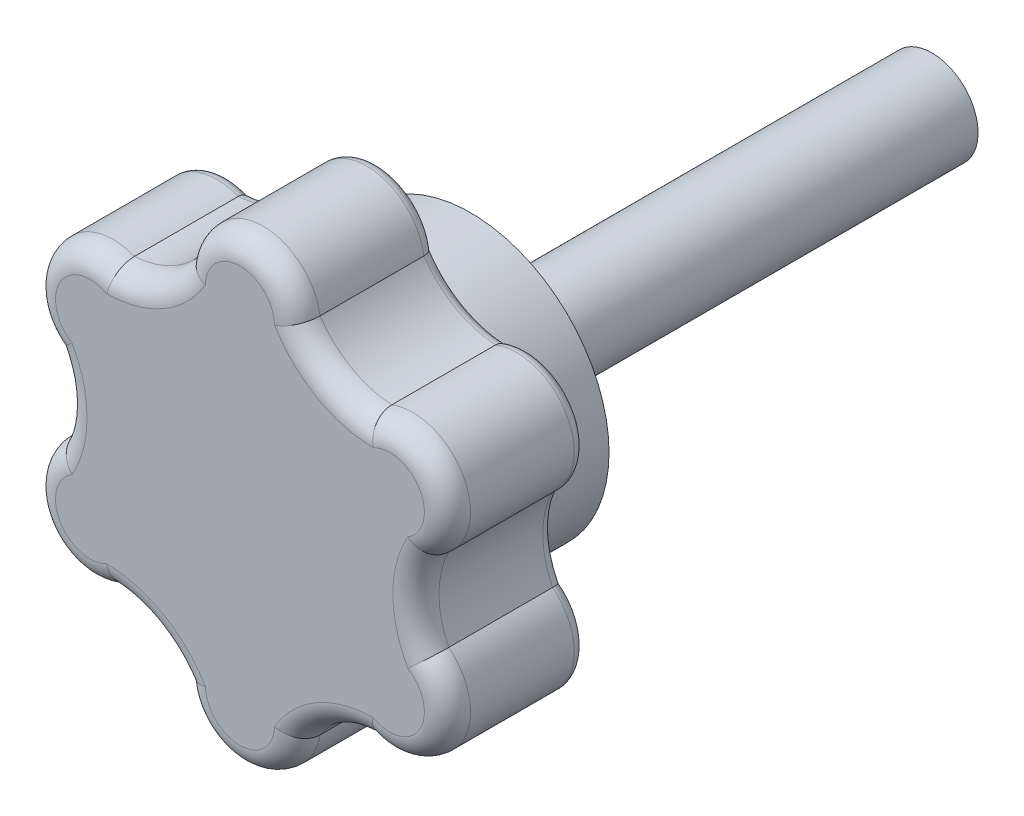
SolidWorks part; units mm, degrees
ref_plane "Front Plane" through (0, 0, 0) normal (0, 0, 1) x (1, 0, 0)
ref_plane "Top Plane" through (0, 0, 0) normal (0, 1, 0) x (1, 0, 0)
ref_plane "Right Plane" through (0, 0, 0) normal (1, 0, 0) x (0, 0, -1)
sketch "Sketch1" plane through (0, 0, 0) normal (0, 0, 1) x (1, 0, 0)
  line L0 (0, 0) -> (0, 28.3956) construction
  circle A0 centre (0, 0) radius 20 construction
  circle A1 centre (0, 0) radius 15 construction
  arc A2 (4.9469, 15.7265) -> (-4.9447, 15.7417) centre (0, 15) ccw
  arc A3 (16.093, 3.5791) -> (11.1603, 12.1531) centre (12.9904, 7.5) ccw
  arc A4 (11.1461, -12.1474) -> (16.105, -3.5886) centre (12.9904, -7.5) ccw
  arc A5 (-4.9469, -15.7265) -> (4.9447, -15.7417) centre (0, -15) ccw
  arc A6 (-16.093, -3.5791) -> (-11.1603, -12.1531) centre (-12.9904, -7.5) ccw
  arc A7 (-11.1461, 12.1474) -> (-16.105, 3.5886) centre (-12.9904, 7.5) ccw
  circle A8 centre (0, 0) radius 16.5 construction
  arc A9 (-16.093, -3.5791) -> (-16.105, 3.5886) centre (-23.289, -0.0073) ccw
  arc A10 (-11.1461, 12.1474) -> (-4.9447, 15.7417) centre (-11.6508, 20.1652) ccw
  arc A11 (4.9469, 15.7265) -> (11.1603, 12.1531) centre (11.6382, 20.1725) ccw
  arc A12 (16.093, 3.5791) -> (16.105, -3.5886) centre (23.289, 0.0073) ccw
  arc A13 (11.1461, -12.1474) -> (4.9447, -15.7417) centre (11.6508, -20.1652) ccw
  arc A14 (-4.9469, -15.7265) -> (-11.1603, -12.1531) centre (-11.6382, -20.1725) ccw
  dimension "D1" = 40
  dimension "D2" = 10
  dimension "D3" = 30
  dimension "D4" = 33
extrude "Extrude2" add sketch "Sketch1" along normal blind 12
sketch "Sketch2" plane through (0, 0, 0) normal (0, 0, -1) x (-1, 0, 0)
  circle A0 centre (0, 0) radius 12
  dimension "D1" = 24
extrude "Extrude3" add sketch "Sketch2" along normal blind 8
sketch "Sketch3" plane through (0, 0, -8) normal (0, 0, -1) x (-1, 0, 0)
  circle A0 centre (0, 0) radius 4
  dimension "D1" = 8
extrude "Extrude4" add sketch "Sketch3" along normal blind 40
fillet "Fillet1" radius 2 12 edges at (0.0077, 20, 12) (7.633, 13.2084, 12) (17.3243, 9.9934, 12) (15.2553, -0.0062, 12) (17.3167, -10.0066, 12) (7.6223, -13.2146, 12) (-0.0077, -20, 12) (-7.633, -13.2084, 12) (-17.3243, -9.9934, 12) (-15.2553, 0.0062, 12) (-17.3167, 10.0066, 12) (-7.6223, 13.2146, 12)
fillet "Fillet2" radius 1 13 edges at (12, 0, 0) (-17.3167, 10.0066, 0) (-15.2553, 0.0062, 0) (-17.3243, -9.9934, 0) (-7.633, -13.2084, 0) (-0.0077, -20, 0) (7.6223, -13.2146, 0) (17.3167, -10.0066, 0) (15.2553, -0.0062, 0) (17.3243, 9.9934, 0) (7.633, 13.2084, 0) (0.0077, 20, 0) (-7.6223, 13.2146, 0)
ref_axis "Axis1" through (0, 0, -48) along (0, 0, 1)
ref_plane "Plane1" through (0, 0, -8) normal (0, 0, -1) x (-1, 0, 0)
